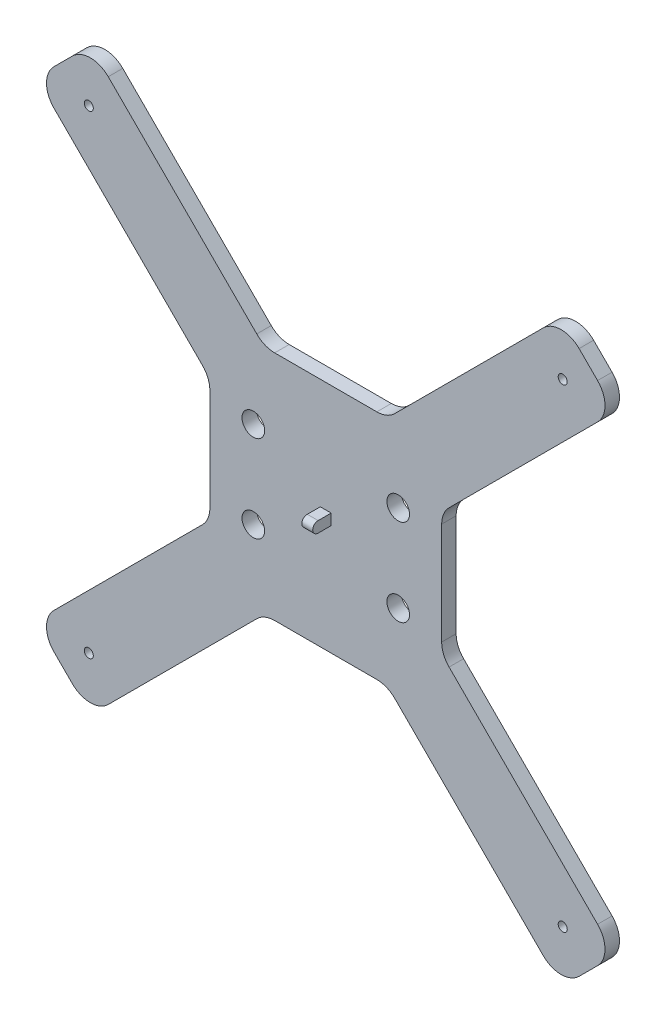
SolidWorks part; units mm, degrees
ref_plane "Front Plane" through (0, 0, 0) normal (0, 0, 1) x (1, 0, 0)
ref_plane "Top Plane" through (0, 0, 0) normal (0, 1, 0) x (1, 0, 0)
ref_plane "Right Plane" through (0, 0, 0) normal (1, 0, 0) x (0, 0, -1)
sketch "Sketch1" plane through (0, 0, 0) normal (0, 0, 1) x (1, 0, 0)
  line L0 (0, 184.15) -> (60.96, 123.19)
  line L5 (19.05, 203.2) -> (80.01, 142.24)
  line L6 (0, 19.05) -> (60.96, 80.01)
  line L7 (19.05, 0) -> (80.01, 60.96)
  line L8 (0, 184.15) -> (19.05, 203.2)
  line L9 (184.15, 203.2) -> (203.2, 184.15)
  line L10 (203.2, 19.05) -> (184.15, 0)
  line L11 (0, 19.05) -> (19.05, 0)
  line L12 (80.01, 142.24) -> (123.19, 142.24)
  line L13 (80.01, 60.96) -> (123.19, 60.96)
  line L14 (60.96, 123.19) -> (60.96, 80.01)
  line L15 (142.24, 123.19) -> (142.24, 80.01)
  line L17 (123.19, 60.96) -> (184.15, 0)
  line L18 (142.24, 80.01) -> (203.2, 19.05)
  line L19 (123.19, 142.24) -> (184.15, 203.2)
  line L20 (142.24, 123.19) -> (203.2, 184.15)
extrude "Boss-Extrude1" add sketch "Sketch1" along normal blind 5.08
fillet "Fillet1" radius 8.89 16 edges at (60.96, 80.01, 2.54) (60.96, 123.19, 2.54) (0, 184.15, 2.54) (19.05, 203.2, 2.54) (80.01, 142.24, 2.54) (123.19, 142.24, 2.54) (184.15, 203.2, 2.54) (203.2, 184.15, 2.54) (142.24, 123.19, 2.54) (142.24, 80.01, 2.54) (203.2, 19.05, 2.54) (184.15, 0, 2.54) (123.19, 60.96, 2.54) (80.01, 60.96, 2.54) (0, 19.05, 2.54) (19.05, 0, 2.54)
sketch "Sketch2" plane through (0, 0, 5.08) normal (0, 0, 1) x (1, 0, 0)
  line L0 (83.6924, 60.96) -> (119.5076, 60.96) construction
  line L1 (119.5076, 142.24) -> (83.6924, 142.24) construction
  line L2 (142.24, 83.6924) -> (142.24, 119.5076) construction
  line L3 (60.96, 119.5076) -> (60.96, 83.6924) construction
  circle A0 centre (127, 86.36) radius 3.9687
  circle A1 centre (127, 116.84) radius 3.9687
  circle A2 centre (76.2, 86.36) radius 3.9687
  circle A3 centre (76.2, 116.84) radius 3.9687
  dimension "D1" = 7.9375
  dimension "D2" = 7.9375
  dimension "D7" = 7.9375
  dimension "D8" = 7.9375
  dimension "D3" = 25.4
  dimension "D4" = 25.4
  dimension "D5" = 15.24
  dimension "D6" = 15.24
  dimension "D9" = 15.24
  dimension "D10" = 15.24
extrude "Cut-Extrude1" cut sketch "Sketch2" against normal through all
sketch "Sketch3" plane through (0, 0, 5.08) normal (0, 0, 1) x (1, 0, 0)
  line L0 (196.9138, 190.4362) -> (190.4362, 196.9138) construction
  line L1 (177.8638, 196.9138) -> (125.7938, 144.8438) construction
  line L4 (12.7638, 196.9138) -> (6.2862, 190.4362) construction
  line L5 (77.4062, 144.8438) -> (25.3362, 196.9138) construction
  line L6 (6.2862, 12.7638) -> (12.7638, 6.2862) construction
  line L7 (25.3362, 6.2862) -> (77.4062, 58.3562) construction
  line L8 (190.4362, 6.2862) -> (196.9138, 12.7638) construction
  line L9 (125.7938, 58.3562) -> (177.8638, 6.2862) construction
  circle A0 centre (184.6888, 184.7007) radius 1.5875
  circle A1 centre (18.5112, 184.7007) radius 1.5875
  circle A2 centre (18.5112, 18.4993) radius 1.5875
  circle A3 centre (184.6888, 18.4993) radius 1.5875
  dimension "D3" = 3.175
  dimension "D6" = 3.175
  dimension "D7" = 3.175
  dimension "D10" = 3.175
  dimension "D1" = 12.7
  dimension "D2" = 13.462
  dimension "D4" = 12.7
  dimension "D5" = 13.462
  dimension "D8" = 12.7
  dimension "D9" = 13.462
  dimension "D11" = 12.7
  dimension "D12" = 13.462
extrude "Cut-Extrude2" cut sketch "Sketch3" against normal through all
ref_plane "Plane1" through (101.6, 0, 0) normal (1, 0, 0) x (0, 0, -1)
sketch "Sketch5" plane through (101.6, 0, 0) normal (1, 0, 0) x (0, 0, -1)
  line L0 (-5.08, 99.695) -> (-5.08, 103.505)
  line L1 (-5.08, 83.6924) -> (-5.08, 119.5076) construction
  line L2 (-5.08, 103.505) -> (-9.652, 103.505)
  line L3 (-9.652, 99.695) -> (-5.08, 99.695)
  arc A0 (-9.652, 103.505) -> (-9.652, 99.695) centre (-9.652, 101.6) ccw
  point P5 (-5.08, 101.6)
  dimension "D1" = 3.81
  dimension "D2" = 4.572
extrude "Boss-Extrude3" add sketch "Sketch5" along normal mid plane 3.81
